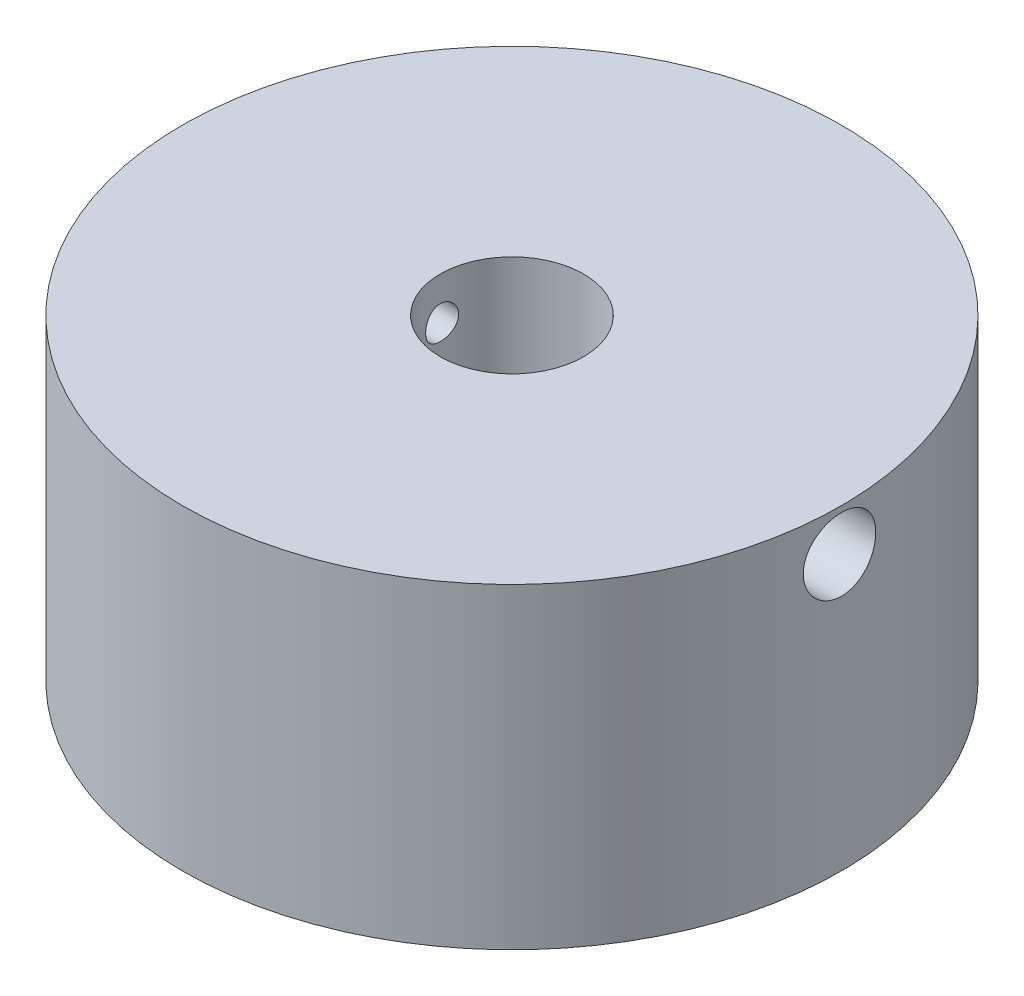
SolidWorks part; units mm, degrees
material "Delrin 2700 NC010, Low Viscosity Acetal Copolymer (SS)"
ref_plane "Front Plane" through (0, 0, 0) normal (0, 0, 1) x (1, 0, 0)
ref_plane "Top Plane" through (0, 0, 0) normal (0, 1, 0) x (1, 0, 0)
ref_plane "Right Plane" through (0, 0, 0) normal (1, 0, 0) x (0, 0, -1)
sketch "Sketch1" plane through (0, 0, 0) normal (0, 1, 0) x (1, 0, 0)
  circle A0 centre (0, 0) radius 79.375
  circle A1 centre (0, 0) radius 17.272
  dimension "D1" = 158.75
  dimension "D2" = 34.544
extrude "Boss-Extrude1" add sketch "Sketch1" along normal blind 76.2
ref_plane "Plane1" through (79.375, 0, 0) normal (-1, 0, 0) x (0, 0, 1)
hole_wizard "CBORE for 3/8 Button Head Cap Screw1" positions "Sketch6" profile "Sketch7" counterbore size "3/8" standard "ANSI Inch" end condition up to next
sketch "Sketch6" plane through (79.375, 0, 0) normal (-1, 0, 0) x (0, 0, 1)
  line L0 (0, 0) -> (0, 76.2) construction
  line L1 (17.272, 76.2) -> (-17.272, 76.2) construction
  point P0 (0, 66.04)
  point P20 (0, 0)
  point P21 (0, 0)
  dimension "D2" = 10.16
sketch "Sketch7" plane through (79.375, 66.04, 0) normal (0, 1, 0) x (0, 0, -1)
  line L0 (0, 0) -> (0, 62.103)
  line L1 (0, 62.103) -> (5.0419, 62.103)
  line L3 (5.0419, 62.103) -> (5.0419, 57.15)
  line L4 (5.0419, 57.15) -> (8.7312, 57.15)
  line L5 (8.7312, 57.15) -> (8.7312, 0)
  line L7 (8.7312, 0) -> (0, 0)
  line L11 (0, -6.35) -> (0, 107.95) construction
  dimension "Thru Hole Dia." = 10.0838
  dimension "Thru Hole Depth" = 62.103
  dimension "C'Bore Dia." = 17.4625
  dimension "C'Bore Depth" = 57.15
hole_wizard "Tap Drill for 3/8-16 Tap1" positions "Sketch18" profile "Sketch19" hole size "3/8-16" standard "ANSI Inch"
sketch "Sketch18" plane through (79.375, 0, 0) normal (-1, 0, 0) x (0, 0, 1)
  point P0 (0, 66.04)
  point P7 (0, 0)
sketch "Sketch19" plane through (79.375, 66.04, 0) normal (0, 1, 0) x (0, 0, -1)
  line L0 (0, 0) -> (0, 109.8267)
  line L1 (0, 109.8267) -> (3.9687, 107.442)
  line L2 (3.9687, 107.442) -> (3.9687, 0)
  line L5 (3.9687, 0) -> (0, 0)
  line L10 (0, 109.8267) -> (-3.9688, 107.442) construction
  line L11 (0, -6.35) -> (0, 107.95) construction
  dimension "Hole Dia." = 7.9375
  dimension "Hole Depth" = 107.442
  dimension "Drill Angle" = 118
ref_plane "Plane4" through (-79.375, 0, 0) normal (-1, 0, 0) x (0, 0, 1)
hole_wizard "CBORE for 3/8 Button Head Cap Screw2" positions "Sketch20" profile "Sketch21" counterbore size "3/8" standard "ANSI Inch" end condition up to next
sketch "Sketch20" plane through (-79.375, 0, 0) normal (-1, 0, 0) x (0, 0, 1)
  line L0 (17.272, 76.2) -> (-17.272, 76.2) construction
  point P0 (0, 10.16)
  point P5 (0, 0)
  dimension "D1" = 66.04
sketch "Sketch21" plane through (-79.375, 10.16, 0) normal (0, 1, 0) x (0, 0, 1)
  line L0 (0, 0) -> (0, 62.103)
  line L1 (0, 62.103) -> (5.0419, 62.103)
  line L3 (5.0419, 62.103) -> (5.0419, 57.15)
  line L4 (5.0419, 57.15) -> (8.7312, 57.15)
  line L5 (8.7312, 57.15) -> (8.7312, 0)
  line L7 (8.7312, 0) -> (0, 0)
  line L11 (0, -6.35) -> (0, 107.95) construction
  dimension "Thru Hole Dia." = 10.0838
  dimension "Thru Hole Depth" = 62.103
  dimension "C'Bore Dia." = 17.4625
  dimension "C'Bore Depth" = 57.15
hole_wizard "Tap Drill for 3/8-16 Tap2" positions "Sketch22" profile "Sketch23" hole size "3/8-16" standard "ANSI Inch"
sketch "Sketch22" plane through (-79.375, 0, 0) normal (-1, 0, 0) x (0, 0, 1)
  point P0 (0, 10.16)
sketch "Sketch23" plane through (-79.375, 10.16, 0) normal (0, 1, 0) x (0, 0, 1)
  line L0 (0, 0) -> (0, 109.8267)
  line L1 (0, 109.8267) -> (3.9687, 107.442)
  line L2 (3.9687, 107.442) -> (3.9687, 0)
  line L5 (3.9687, 0) -> (0, 0)
  line L10 (0, 109.8267) -> (-3.9688, 107.442) construction
  line L11 (0, -6.35) -> (0, 107.95) construction
  dimension "Hole Dia." = 7.9375
  dimension "Hole Depth" = 107.442
  dimension "Drill Angle" = 118
